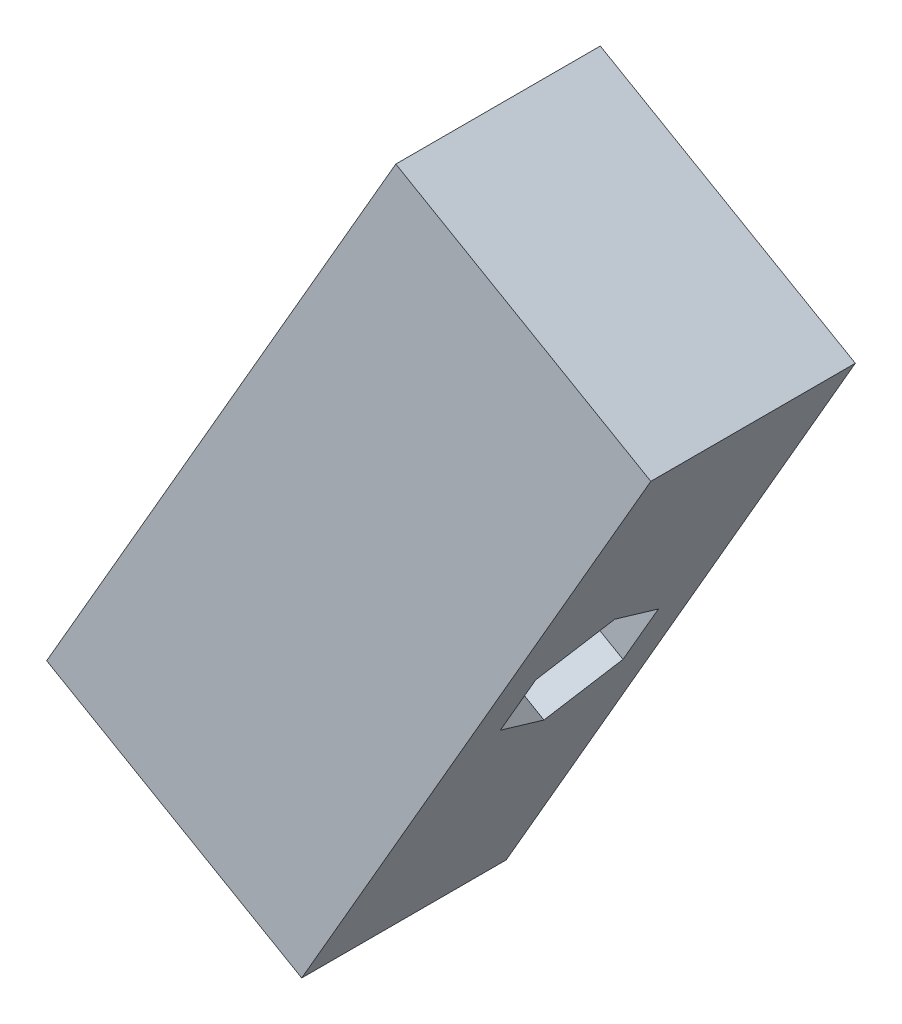
SolidWorks part; units mm, degrees
ref_plane "Plano frontal" through (0, 0, 0) normal (0, 0, 1) x (1, 0, 0)
ref_plane "Plano superior" through (0, 0, 0) normal (0, 1, 0) x (1, 0, 0)
ref_plane "Plano direito" through (0, 0, 0) normal (1, 0, 0) x (0, 0, -1)
sketch "Esboço2" plane through (0, 0, 0) normal (0, 0, 1) x (1, 0, 0)
  line L0 (-37.2265, 1.433) -> (-19.8542, 31.5226) construction
  line L1 (-37.2265, 1.433) -> (-50.2168, 8.933) construction
  line L2 (-19.8542, 31.5226) -> (-32.8446, 39.0226) construction
  line L3 (-50.2168, 8.933) -> (-32.8446, 39.0226) construction
  line L4 (-49.807, 9.0428) -> (-32.7348, 38.6128)
  line L5 (-20.264, 31.4128) -> (-32.7348, 38.6128)
  line L6 (-37.3363, 1.8428) -> (-20.264, 31.4128)
  line L7 (-37.3363, 1.8428) -> (-49.807, 9.0428)
  line L16 (-13.6861, -47.9555) -> (13.6861, -47.9555) construction
  line L17 (-13.6861, -50.9555) -> (-13.6861, -47.9555) construction
  line L18 (-17.3722, -50.9555) -> (-13.6861, -50.9555) construction
  line L19 (-17.3722, -32.9555) -> (-17.3722, -50.9555) construction
  line L20 (17.3722, -32.9555) -> (-17.3722, -32.9555) construction
  line L21 (17.3722, -50.9555) -> (17.3722, -32.9555) construction
  line L22 (13.6861, -50.9555) -> (17.3722, -50.9555) construction
  line L23 (13.6861, -47.9555) -> (13.6861, -50.9555) construction
  line L32 (-48.3738, 12.1253) -> (-50.9718, 13.6253) construction
  line L33 (-34.6877, 35.8303) -> (-48.3738, 12.1253) construction
  line L34 (-37.2858, 37.3303) -> (-34.6877, 35.8303) construction
  line L35 (-35.4427, 40.5226) -> (-37.2858, 37.3303) construction
  line L36 (-19.8542, 31.5226) -> (-35.4427, 40.5226) construction
  line L37 (-37.2265, 1.433) -> (-19.8542, 31.5226) construction
  line L38 (-52.8149, 10.433) -> (-37.2265, 1.433) construction
  line L39 (-50.9718, 13.6253) -> (-52.8149, 10.433) construction
  line L48 (34.6877, 35.8303) -> (37.2858, 37.3303) construction
  line L49 (48.3738, 12.1253) -> (34.6877, 35.8303) construction
  line L50 (50.9718, 13.6253) -> (48.3738, 12.1253) construction
  line L51 (52.8149, 10.433) -> (50.9718, 13.6253) construction
  line L52 (37.2265, 1.433) -> (52.8149, 10.433) construction
  line L53 (19.8542, 31.5226) -> (37.2265, 1.433) construction
  line L54 (35.4427, 40.5226) -> (19.8542, 31.5226) construction
  line L55 (37.2858, 37.3303) -> (35.4427, 40.5226) construction
  line L60 (-40.9264, 45.0245) -> (-59.4555, 12.9311) construction
  line L61 (-59.4555, 12.9311) -> (-18.5291, -57.9555) construction
  line L62 (-18.5291, -57.9555) -> (18.5291, -57.9555) construction
  line L63 (18.5291, -57.9555) -> (59.4555, 12.9311) construction
  line L64 (59.4555, 12.9311) -> (40.9264, 45.0245) construction
  line L65 (40.9264, 45.0245) -> (-40.9264, 45.0245) construction
  circle A2 centre (0, 0) radius 12.5 construction
  dimension "D1" = 0.3
extrude "Ressalto-extrusão1" add sketch "Esboço2" along normal blind 10
sketch "Esboço3" plane through (-41.2709, 23.8278, 0) normal (-0.866, 0.5, 0) x (0, 0, 1)
  line L0 (0, 0) -> (10, 0) construction
  line L1 (0, 17.0722) -> (0, -17.0722) construction
  line L2 (10, 17.0722) -> (10, -17.0722) construction
  line L3 (7.6882, 1.6194) -> (4.9882, 3.1782) construction
  line L4 (4.9882, 3.1782) -> (2.2882, 1.6194) construction
  line L5 (2.2882, 1.6194) -> (2.2882, -1.4983) construction
  line L6 (2.2882, -1.4983) -> (4.9882, -3.0572) construction
  line L7 (4.9882, -3.0572) -> (7.6882, -1.4983) construction
  line L8 (7.6882, -1.4983) -> (7.6882, 1.6194) construction
  line L9 (4.9882, 3.5246) -> (1.9882, 1.7926)
  line L10 (1.9882, 1.7926) -> (1.9882, -1.6715)
  line L11 (1.9882, -1.6715) -> (4.9882, -3.4036)
  line L12 (4.9882, -3.4036) -> (7.9882, -1.6715)
  line L13 (7.9882, -1.6715) -> (7.9882, 1.7926)
  line L14 (7.9882, 1.7926) -> (4.9882, 3.5246)
  circle A0 centre (5, 0) radius 1.5 construction
  circle A1 centre (5, 0) radius 1.7
  circle A2 centre (4.9882, 0.0605) radius 2.7 construction
  point P10 (0, 0)
  point P19 (0, 0)
  dimension "D1" = 3
  dimension "D2" = 0.2
  dimension "D3" = 0.3
extrude "Corte-extrusão1" cut sketch "Esboço3" against normal through all contours A1 region at (-41.2709, 23.8278, 5)
extrude "Corte-extrusão3" cut sketch "Esboço3<4>" along normal blind 3 from surface starting at face at (-29.6502, 15.1555, 5)
sketch "Esboço3<4>" plane through (-41.2709, 23.8278, 0) normal (-0.866, 0.5, 0) x (0, 0, 1) same geometry as "Esboço3"
